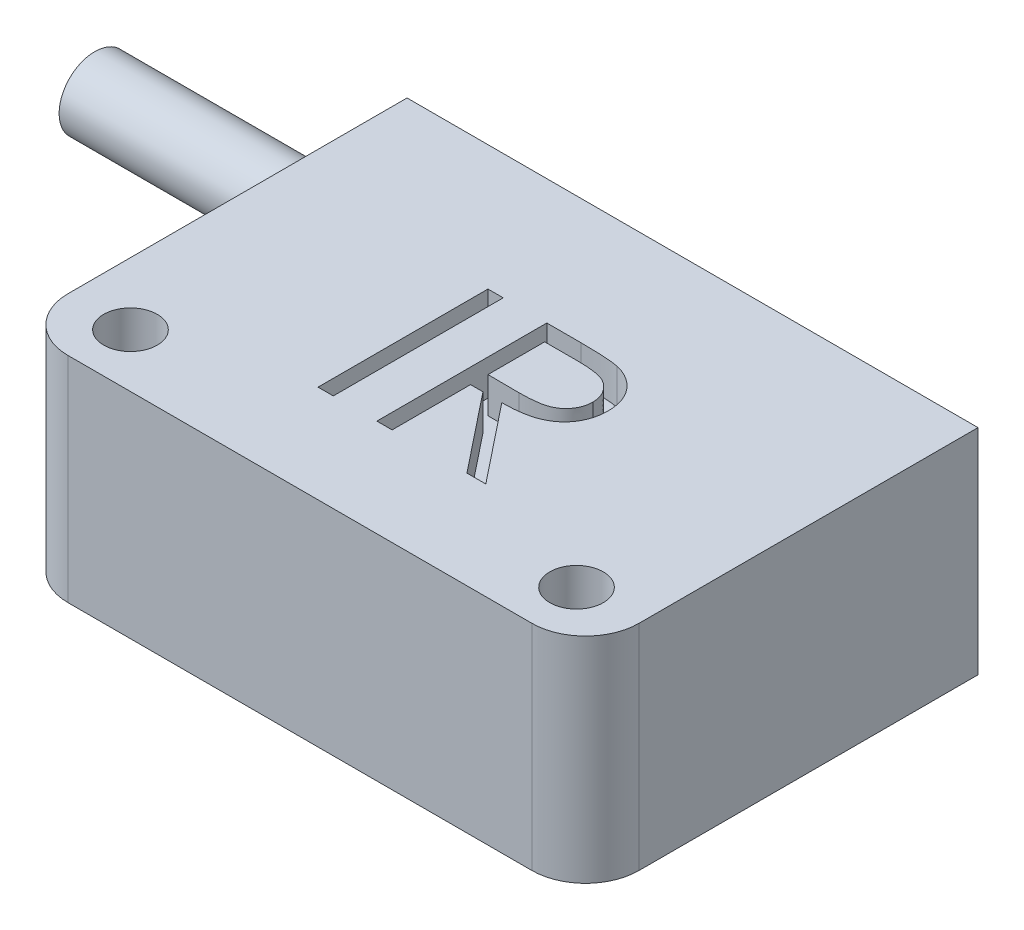
SolidWorks part; units mm, degrees
ref_plane "Front Plane" through (0, 0, 0) normal (0, 0, 1) x (1, 0, 0)
ref_plane "Top Plane" through (0, 0, 0) normal (0, 1, 0) x (1, 0, 0)
ref_plane "Right Plane" through (0, 0, 0) normal (1, 0, 0) x (0, 0, -1)
sketch "Sketch1" plane through (0, 0, 0) normal (0, 1, 0) x (1, 0, 0)
  line L1 (0, 0) -> (32, 0)
  line L2 (0, 0) -> (0, 22)
  line L3 (0, 22) -> (32, 22)
  line L4 (32, 0) -> (32, 22)
  dimension "D1" = 32
  dimension "D2" = 22
extrude "Boss-Extrude1" add sketch "Sketch1" along normal blind 12
sketch "Sketch2" plane through (0, 0, 0) normal (-1, 0, 0) x (0, 0, 1)
  line L0 (-22, 6) -> (0, 6) construction
  line L1 (-22, 12) -> (-22, 0) construction
  line L2 (0, 12) -> (0, 0) construction
  line L3 (-19.5, 12) -> (-19.5, 0) construction
  line L4 (-22, 12) -> (0, 12) construction
  line L5 (-22, 0) -> (0, 0) construction
  circle A0 centre (-19.5, 6) radius 2
  dimension "D1" = 4
  dimension "D2" = 2.5
extrude "Boss-Extrude2" add sketch "Sketch2" along normal blind 15
sketch "Sketch3" plane through (0, 12, 0) normal (0, 1, 0) x (1, 0, 0)
  line L12 (3.5, 3) -> (28.5, 3) construction
  line L13 (16, 3) -> (16, 22) construction
  line L14 (32, 22) -> (0, 22) construction
  line L15 (0, 0) -> (32, 0) construction
  circle A0 centre (3.5, 3) radius 1.5
  circle A1 centre (28.5, 3) radius 1.5
  dimension "D3" = 3
  dimension "D1" = 3
  dimension "D2" = 25
extrude "Cut-Extrude1" cut sketch "Sketch3" against normal through all contours A0 | A0 | A1 | A1 region at (3.5, 12, -3) region at (28.5, 12, -3)
sketch "Sketch4" plane through (0, 12, 0) normal (0, 1, 0) x (1, 0, 0)
  line L0 (0, 5.469) -> (32, 5.469) construction
  line L1 (0, 22) -> (0, 0) construction
  line L2 (32, 0) -> (32, 22) construction
  text T0 "IR" font "Century Gothic" height in points 36
extrude "Cut-Extrude2" cut sketch "Sketch4" against normal blind 2
split "Split1" bodies to split 104 resulting bodies 105 106 split by face at (0, 6, -21.5)
fillet "Fillet1" radius 3 2 edges at (32, 6, 0) (0, 6, 0)
